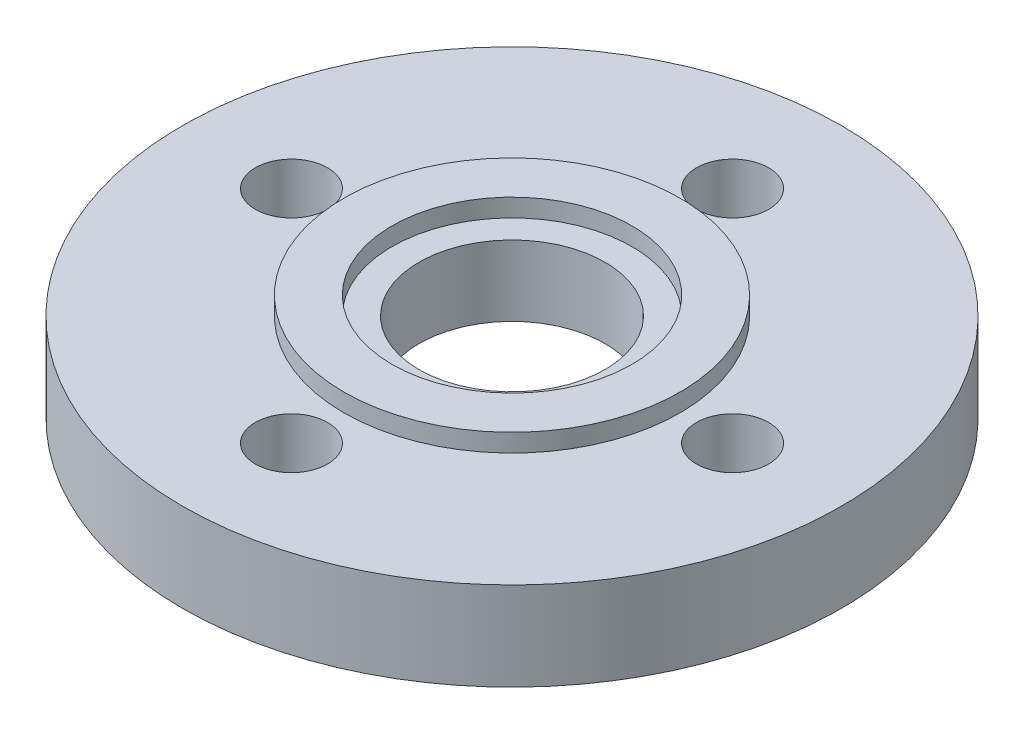
SolidWorks part; units mm, degrees
ref_plane "Alzado" through (0, 0, 0) normal (0, 0, 1) x (1, 0, 0)
ref_plane "Planta" through (0, 0, 0) normal (0, 1, 0) x (1, 0, 0)
ref_plane "Vista lateral" through (0, 0, 0) normal (1, 0, 0) x (0, 0, -1)
sketch "Croquis base" plane through (0, 0, 0) normal (0, 1, 0) x (1, 0, 0)
  line L0 (-10.9823, 0) -> (10.9823, 0) construction
  circle A0 centre (0, 0) radius 10.9823
  circle A1 centre (0, 0) radius 4.95
  circle A2 centre (0, 0) radius 3
  circle A3 centre (-7.35, 0) radius 1.2028
  circle A4 centre (0, 7.35) radius 1.2028
  circle A5 centre (7.35, 0) radius 1.2028
  circle A6 centre (0, -7.35) radius 1.2028
  dimension "D1" = 7.35
  dimension "D2" = 4
extrude "Saliente-Extruir1" add sketch "Croquis base" along normal blind 2.95 contours A0
extrude "Cortar-Extruir1" cut sketch "Croquis base<3>" along normal through all and the other way through all contours A5 | A4 | A2 | A3 | A6
sketch "Croquis base<3>" plane through (0, 0, 0) normal (0, 1, 0) x (1, 0, 0) same geometry as "Croquis base"
extrude "Cortar-Extruir2" cut sketch "Croquis base<4>" along normal blind 0.6 contours A1
sketch "Croquis base<4>" plane through (0, 0, 0) normal (0, 1, 0) x (1, 0, 0) same geometry as "Croquis base"
sketch "Croquis2" plane through (0, 2.95, 0) normal (0, 1, 0) x (1, 0, 0)
  circle A0 centre (0, 0) radius 5.6
  dimension "D1" = 11.2
extrude "Saliente-Extruir2" add sketch "Croquis2" along normal blind 0.6
sketch "Croquis3" plane through (0, 3.55, 0) normal (0, 1, 0) x (1, 0, 0)
  circle A0 centre (0, 0) radius 3.1
  circle A1 centre (0, 0) radius 4
  dimension "D1" = 6.2
  dimension "D2" = 8
extrude "Cortar-Extruir3" cut sketch "Croquis3" against normal through all contours A0
extrude "Cortar-Extruir4" cut sketch "Croquis3<3>" against normal blind 0.6 contours A1
sketch "Croquis3<3>" plane through (0, 3.55, 0) normal (0, 1, 0) x (1, 0, 0) same geometry as "Croquis3"
